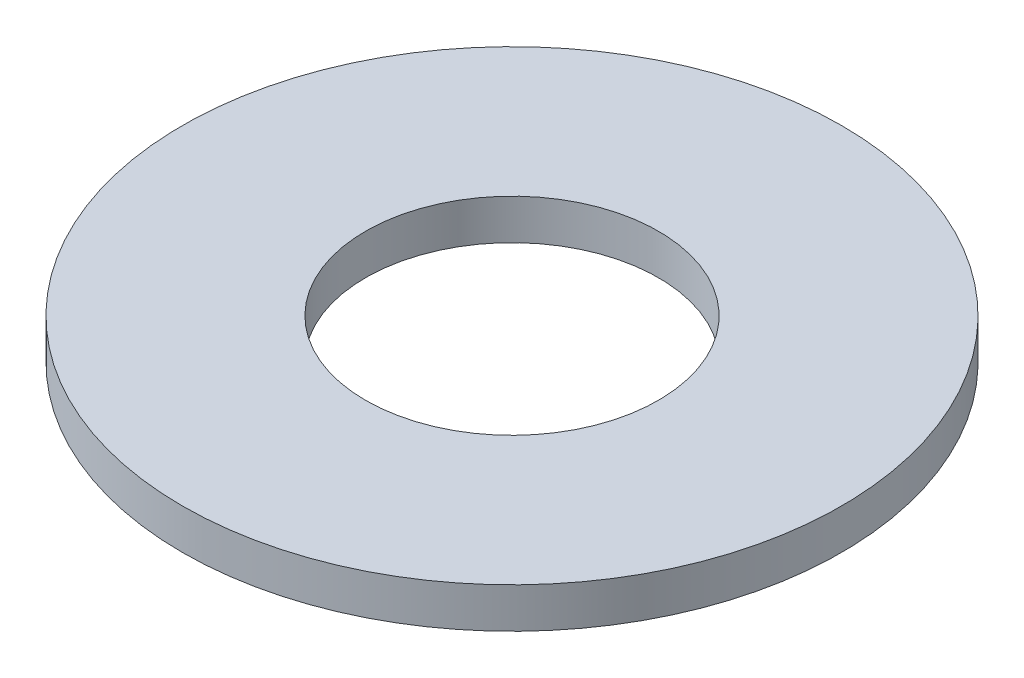
SolidWorks part; units mm, degrees
ref_plane "Front Plane" through (0, 0, 0) normal (0, 0, 1) x (1, 0, 0)
ref_plane "Top Plane" through (0, 0, 0) normal (0, 1, 0) x (1, 0, 0)
ref_plane "Right Plane" through (0, 0, 0) normal (1, 0, 0) x (0, 0, -1)
sketch "Sketch1" plane through (0, 0, 0) normal (0, 1, 0) x (1, 0, 0)
  circle A0 centre (0, 0) radius 90
  dimension "FLANGE_OD" = 180
extrude "Boss-Extrude1" add sketch "Sketch1" along normal blind 11
sketch "Sketch2" plane through (0, 0, 0) normal (0, 1, 0) x (1, 0, 0)
  circle A0 centre (0, 0) radius 40
  dimension "BORE_D" = 80
extrude "Cut-Extrude1" cut sketch "Sketch2" along normal through all
sketch "Sketch3" plane through (0, 11, 0) normal (0, 1, 0) x (1, 0, 0)
  circle A0 centre (0, 0) radius 32.2664 construction
  circle A1 centre (-32.2664, 0) radius 4.2919
  dimension "BOLT_D" = 8.5838
  dimension "BOLT_PCD" = 64.5328
extrude "Cut-Extrude2" cut sketch "Sketch3" against normal blind 8.6186 rebuild error yes
pattern_circular "CirPattern1" count 3 over 360 rebuild error yes
